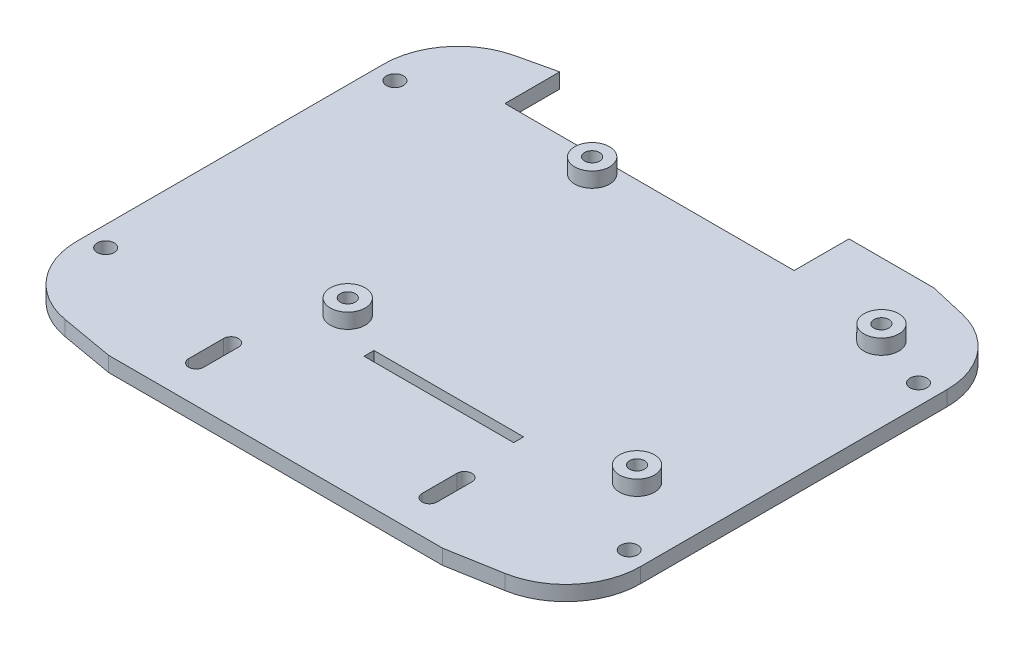
SolidWorks part; units mm, degrees
note: The reader was unsure of these and kept them because the rebuilt part matched: shared geometry of "Esquisse8<3>".
ref_plane "Plan de face" through (0, 0, 0) normal (0, 0, 1) x (1, 0, 0)
ref_plane "Plan de dessus" through (0, 0, 0) normal (0, 1, 0) x (1, 0, 0)
ref_plane "Plan de droite" through (0, 0, 0) normal (1, 0, 0) x (0, 0, -1)
sketch "Esquisse1" plane through (0, 0, 0) normal (0, 1, 0) x (1, 0, 0)
  line L0 (-33.922, -73) -> (33.922, -73) construction
  line L3 (-37.5, 95) -> (37.5, 95)
  line L4 (37.5, 51) -> (37.5, 95)
  line L5 (0, 0) -> (37.5, 95) construction
  line L6 (-21, -61.9) -> (-21, -66.9) construction
  line L7 (0, 95) -> (0, -95) construction
  line L8 (37.5, 51) -> (44.8743, 49.2975)
  line L9 (-24, -61.9) -> (-24, -66.9) construction
  line L10 (56.5, 34.682) -> (56.5, -26.8)
  line L11 (44.1047, -41.5721) -> (17, -46.3514)
  line L12 (22.5, -54.5324) -> (22.5, -84.1) construction
  line L13 (42.569, 51.5625) -> (42.569, 95.5625) construction
  line L14 (-8.1306, -79.1) -> (-42.569, -79.1) construction
  line L15 (56.5, -39.3865) -> (56.5, -125.6461) construction
  line L16 (-17, -95) -> (17, -95)
  line L17 (0, 0) -> (18.2122, -46.1377) construction
  line L18 (-56.5, 51) -> (56.5, 51) construction
  line L19 (-8.1306, -66.9) -> (-42.569, -66.9) construction
  line L20 (-33.922, -79.1) -> (-33.922, -66.9) construction
  line L24 (0, 0) -> (-18.2122, -46.1377) construction
  line L25 (-56.5, -39.3865) -> (-56.5, -125.6461) construction
  line L26 (33.922, -79.1) -> (33.922, -66.9) construction
  line L27 (8.1306, -66.9) -> (42.569, -66.9) construction
  line L28 (8.1306, -79.1) -> (42.569, -79.1) construction
  line L29 (17, -66.9) -> (27, -66.9)
  line L30 (27, -66.9) -> (27, -61.9)
  line L31 (27, -61.9) -> (17, -61.9)
  line L32 (24, -61.9) -> (24, -66.9) construction
  line L33 (21, -61.9) -> (21, -66.9) construction
  line L34 (27, -84.1) -> (17, -84.1)
  line L35 (17, -79.1) -> (27, -79.1)
  line L36 (27, -79.1) -> (27, -84.1)
  line L37 (17, -66.9) -> (17, -79.1)
  line L38 (17, -84.1) -> (17, -95)
  line L39 (17, -61.9) -> (17, -46.3514)
  line L40 (-42.569, 51.5625) -> (-42.569, 95.5625) construction
  line L41 (-22.5, -54.5324) -> (-22.5, -84.1) construction
  line L42 (0, 0) -> (-37.5, 95) construction
  line L44 (-17, -61.9) -> (-17, -46.3514)
  line L45 (-17, -84.1) -> (-17, -95)
  line L46 (-17, -66.9) -> (-17, -79.1)
  line L47 (-27, -79.1) -> (-27, -84.1)
  line L48 (-17, -79.1) -> (-27, -79.1)
  line L49 (-27, -84.1) -> (-17, -84.1)
  line L50 (-27, -61.9) -> (-17, -61.9)
  line L51 (-27, -66.9) -> (-27, -61.9)
  line L52 (-17, -66.9) -> (-27, -66.9)
  line L53 (-44.1047, -41.5721) -> (-17, -46.3514)
  line L54 (-56.5, 34.682) -> (-56.5, -26.8)
  line L55 (-37.5, 51) -> (-44.8743, 49.2975)
  line L56 (-37.5, 51) -> (-37.5, 95)
  arc A2 (56.5, -26.8) -> (44.1047, -41.5721) centre (41.5, -26.8) cw
  arc A3 (44.8743, 49.2975) -> (56.5, 34.682) centre (41.5, 34.682) cw
  arc A4 (-44.8743, 49.2975) -> (-56.5, 34.682) centre (-41.5, 34.682) ccw
  arc A5 (-56.5, -26.8) -> (-44.1047, -41.5721) centre (-41.5, -26.8) ccw
  point P0 (0, 0)
  point P16 (0, 51)
  point P33 (33.922, -73)
  point P52 (0, 51)
  point P53 (-56.5, 46.6135)
  point P62 (0, -73)
  point P69 (-33.922, -73)
  point P78 (56.5, 46.6135)
  point P87 (33.922, -73)
  point P88 (-33.922, -73)
  point P89 (56.5, 46.6135)
  dimension "D2" = 10
  dimension "D3" = 190
  dimension "D4" = 34
  dimension "D5" = 13
  dimension "D6" = 56.5
  dimension "D7" = 86
  dimension "D8" = 12.2
  dimension "D9" = 10
  dimension "D10" = 3
  dimension "D11" = 3
  dimension "D16" = 44
extrude "Boss.-Extru.1" add sketch "Esquisse1" along normal blind 3 contours L3 L4 L8 A3 L10 A2 L11 L39 L31 L30 L29 L37 L35 L36 L34 L38 L16 L45 L49 L47 L48 L46 L52 L51 L50 L44 L53 A5 L54 A4 L55 L56
fillet "Congé1" radius 20 2 edges at (17, 1.5, 46.3514) (-17, 1.5, 46.3514)
fillet "Congé2" radius 5 2 edges at (17, 1.5, 61.9) (-17, 1.5, 61.9)
sketch "Esquisse2" plane through (0, 0, 84.1) normal (0, 0, 1) x (1, 0, 0)
  line L0 (0, 17.1398) -> (0, -10.9487) construction
  line L1 (-27, 5) -> (-27, 8.9044)
  line L2 (-27, 8.9044) -> (-16.8331, 8.9044)
  line L3 (-16.8331, 8.9044) -> (-14.4276, 3)
  line L4 (-17, 3) -> (17, 3) construction
  line L6 (-17, 0) -> (17, 0) construction
  line L7 (-14.4276, 0) -> (-27, 0)
  line L8 (-27, 0) -> (-27, 5)
  line L9 (-14.4276, 3) -> (-14.4276, 0)
  line L10 (16.8331, 8.9044) -> (14.4276, 3)
  line L11 (27, 8.9044) -> (16.8331, 8.9044)
  line L12 (27, 5) -> (27, 8.9044)
  line L13 (27, 0) -> (27, 5)
  line L14 (14.4276, 0) -> (27, 0)
  line L15 (14.4276, 3) -> (14.4276, 0)
extrude "Boss.-Extru.2" add sketch "Esquisse2" against normal blind 5
ref_plane "Plan1" through (0, 0, 73) normal (0, 0, 1) x (1, 0, 0)
mirror "Symétrie1" about plane through (0, 0, 73) normal (0, 0, 1) of "Boss.-Extru.2"
fillet "Congé4" radius 2 8 edges at (-16.8331, 8.9044, 81.6) (-14.4276, 3, 81.6) (-16.8331, 8.9044, 64.4) (-14.4276, 3, 64.4) (16.8331, 8.9044, 64.4) (16.8331, 8.9044, 81.6) (14.4276, 3, 64.4) (14.4276, 3, 81.6)
fillet "Congé5" radius 4 10 edges at (27, 8.9044, 81.6) (-27, 8.9044, 81.6) (27, 8.9044, 64.4) (-27, 8.9044, 64.4) (-25.1606, 0, 61.9) (-27, 0, 64.4) (-27, 0, 81.6) (27, 0, 81.6) (27, 0, 64.4) (25.1606, 0, 61.9)
sketch "Esquisse3" plane through (0, 0, 84.1) normal (0, 0, 1) x (1, 0, 0)
  line L0 (-27, 4.4522) -> (-17, 4.4522) construction
  line L3 (-22, 4.4522) -> (-22, 7.1928) construction
  line L4 (0, 9.9913) -> (0, -3.4658) construction
  circle A0 centre (-22, 4.4522) radius 1.5
  circle A1 centre (22, 4.4522) radius 1.5
  dimension "D1" = 3
extrude "Enlèv. mat.-Extru.2" cut sketch "Esquisse3" against normal blind 25
sketch "Esquisse4" plane through (0, 3, 0) normal (0, 1, 0) x (1, 0, 0)
  line L0 (-17, -90.8) -> (17, -90.8) construction
  line L2 (17, -84.1) -> (17, -95) construction
  line L3 (-17, -95) -> (17, -95) construction
  line L4 (-55, -73) -> (55, -73) construction
  line L5 (-8.9067, -81.172) -> (8.9067, -81.172)
  line L6 (-8.9067, -81.172) -> (-8.9067, -64.828)
  line L7 (-8.9067, -64.828) -> (8.9067, -64.828)
  line L8 (8.9067, -81.172) -> (8.9067, -64.828)
  line L9 (-8.9067, -81.172) -> (8.9067, -64.828) construction
  line L10 (-8.9067, -64.828) -> (8.9067, -81.172) construction
  line L11 (0, -87.4088) -> (0, -95) construction
  circle A0 centre (-10, -90.8) radius 1.7
  circle A1 centre (10, -90.8) radius 1.7
  circle A2 centre (8.9067, -64.828) radius 1.7
  circle A3 centre (8.9067, -81.172) radius 1.7
  circle A4 centre (-8.9067, -81.172) radius 1.7
  circle A5 centre (-8.9067, -64.828) radius 1.7
  point P12 (0, -73)
  dimension "D2" = 3.4
  dimension "D3" = 3.4
  dimension "D1" = 4.2
  dimension "D4" = 10
  dimension "D5" = 10
  dimension "D6" = 17.8135
  dimension "D7" = 16.344
extrude "Enlèv. mat.-Extru.3" cut sketch "Esquisse4" against normal blind 25 contours A4 | A3 | A2 | A5 | A0 | A1
sketch "Esquisse5" plane through (0, 3, 0) normal (0, 1, 0) x (1, 0, 0)
  line L0 (37.5, 51) -> (37.5, 95) construction
  line L1 (48.5019, 75) -> (-37.5, 75) construction
  line L2 (39.0019, 53) -> (58.0019, 53) construction
  line L3 (39.0019, 53) -> (39.0019, 97) construction
  line L4 (39.0019, 97) -> (58.0019, 97) construction
  line L5 (58.0019, 53) -> (58.0019, 97) construction
  line L6 (39.0019, 53) -> (58.0019, 97) construction
  line L7 (39.0019, 97) -> (58.0019, 53) construction
  line L8 (-37.5, 51) -> (-37.5, 95) construction
  line L9 (-37.5, 95) -> (37.5, 95) construction
  line L10 (15.5, 75) -> (15.5, 83) construction
  line L11 (27.5, 95) -> (27.5, 38.0482) construction
  line L12 (15.5, 75) -> (15.5, 49) construction
  line L13 (-27.5, 95) -> (-27.5, 53) construction
  line L14 (-13, 83) -> (-13, 67) construction
  line L15 (-13, 83) -> (15.5, 83) construction
  line L16 (-27.5, 89) -> (27.5, 89) construction
  circle A0 centre (15.5, 83) radius 1.7
  circle A1 centre (15.5, 49) radius 1.7
  circle A2 centre (-13, 83) radius 1.7
  circle A3 centre (-13, 67) radius 1.7
  circle A4 centre (27.5, 80) radius 1.7
  circle A5 centre (27.5, 55) radius 1.7
  circle A6 centre (27.5, 89) radius 1.7
  circle A7 centre (-27.5, 89) radius 1.7
  circle A8 centre (-27.5, 80) radius 1.7
  circle A9 centre (-27.5, 55) radius 1.7
  circle A10 centre (0, 89) radius 1.7
  point P3 (48.5019, 75)
  point P26 (-13, 75)
  dimension "D5" = 26
  dimension "D7" = 3.4
  dimension "D10" = 22
  dimension "D13" = 10
  dimension "D14" = 6
  dimension "D16" = 40
  dimension "D17" = 6
  dimension "D20" = 3.4
  dimension "D1" = 75
  dimension "D2" = 19
  dimension "D3" = 44
  dimension "D4" = 20
  dimension "D6" = 28.5
  dimension "D8" = 8
  dimension "D9" = 16
  dimension "D11" = 24.5
  dimension "D12" = 10
  dimension "D15" = 15
  dimension "D18" = 15
  dimension "D19" = 40
extrude "Enlèv. mat.-Extru.4" cut sketch "Esquisse5" against normal blind 10
sketch "Esquisse6" plane through (0, 3, 0) normal (0, 1, 0) x (1, 0, 0)
  line L0 (-52.4847, -25.059) -> (-52.4847, 32.941) construction
  line L1 (-56.5, 34.682) -> (-56.5, -26.8) construction
  line L2 (-56.5, 3.941) -> (56.5, 3.941) construction
  line L3 (56.5, 34.682) -> (56.5, -26.8) construction
  line L4 (0, 53.7621) -> (0, -51.3081) construction
  line L5 (52.4847, -25.059) -> (52.4847, 32.941) construction
  circle A0 centre (-52.4847, 32.941) radius 1.7
  circle A1 centre (-52.4847, -25.059) radius 1.7
  circle A2 centre (52.4847, -25.059) radius 1.7
  circle A3 centre (52.4847, 32.941) radius 1.7
  point P9 (-52.4847, 3.941)
  dimension "D2" = 3.4
  dimension "D1" = 58
extrude "Enlèv. mat.-Extru.5" cut sketch "Esquisse6" against normal blind 10
fillet "Congé6" radius 10 2 edges at (-37.5, 1.5, -95) (37.5, 1.5, -95)
sketch "Esquisse7" plane through (0, 3, 0) normal (0, 1, 0) x (1, 0, 0)
  line L0 (-86.4549, 51) -> (-37.5, 51)
  line L1 (-86.4549, 51) -> (-47.0507, 103.2271)
  line L2 (-47.0507, 103.2271) -> (68.271, 103.2271)
  line L3 (68.271, 103.2271) -> (91.5248, 51)
  line L4 (-37.5, 51) -> (-37.5, 40)
  line L5 (20.5, 51) -> (20.5, 40)
  line L6 (-37.5, 40) -> (20.5, 40)
  line L7 (20.5, 51) -> (91.5248, 51)
  line L8 (-33.4885, -43.444) -> (33.4885, -43.444)
  line L9 (33.4885, -43.444) -> (53.128, -56.1621)
  line L10 (53.128, -56.1621) -> (47.4978, -107.9067)
  line L11 (47.4978, -107.9067) -> (-41.2455, -107.9067)
  line L12 (-41.2455, -107.9067) -> (-59.4767, -77.0744)
  line L13 (-59.4767, -77.0744) -> (-33.4885, -43.444)
  dimension "D1" = 11
  dimension "D2" = 17
extrude "Enlèv. mat.-Extru.8" cut sketch "Esquisse7" against normal mid plane 20
sketch "Esquisse8" plane through (0, 3, 0) normal (0, 1, 0) x (1, 0, 0)
  line L0 (0, -16) -> (0, 40) construction
  line L1 (-56.5, 12) -> (56.5, 12) construction
  line L2 (56.5, -16) -> (-56.5, -16) construction
  line L3 (56.5, 34.682) -> (56.5, -26.8) construction
  line L4 (-56.5, 34.682) -> (-56.5, -26.8) construction
  line L5 (20.5, 40) -> (-37.5, 40) construction
  line L6 (0, 40) -> (0, -16) construction
  line L7 (-16.5, 36.5) -> (41.5, 36.5) construction
  line L8 (-16.5, 36.5) -> (-16.5, -12.5) construction
  line L9 (-16.5, -12.5) -> (41.5, -12.5) construction
  line L10 (41.5, 36.5) -> (41.5, -12.5) construction
  line L11 (-16.5, 36.5) -> (41.5, -12.5) construction
  line L12 (-16.5, -12.5) -> (41.5, 36.5) construction
  line L13 (-45, 40) -> (45, 40) construction
  line L14 (-45, 40) -> (-45, -16) construction
  line L15 (-45, -16) -> (45, -16) construction
  line L16 (45, 40) -> (45, -16) construction
  line L17 (-45, 40) -> (45, -16) construction
  line L18 (-45, -16) -> (45, 40) construction
  line L19 (45, 12) -> (-45, 12) construction
  line L20 (0, -18) -> (0, -43.444) construction
  line L21 (22.2657, -16) -> (-7.7343, -16)
  line L22 (22.2657, -16) -> (22.2657, -18)
  line L23 (22.2657, -18) -> (-7.7343, -18)
  line L24 (-7.7343, -16) -> (-7.7343, -18)
  line L25 (-33.4885, -43.444) -> (33.4885, -43.444) construction
  circle A0 centre (41.5, 36.5) radius 1.5
  circle A1 centre (41.5, -12.5) radius 1.5
  circle A2 centre (-16.5, -12.5) radius 1.5
  circle A3 centre (-16.5, 36.5) radius 1.5
  circle A4 centre (41.5, -12.5) radius 3.5
  circle A5 centre (41.5, 36.5) radius 3.5
  circle A6 centre (-16.5, -12.5) radius 3.5
  circle A7 centre (-16.5, 36.5) radius 3.5
  point P13 (12.5, 12)
  point P24 (0, 12)
  point P32 (0, 12)
  point P43 (0, -18)
  dimension "D4" = 3
  dimension "D1" = 56
  dimension "D2" = 58
  dimension "D3" = 49
  dimension "D5" = 90
  dimension "D6" = 56
  dimension "D7" = 3.5
  dimension "D8" = 2
  dimension "D9" = 30
extrude "Enlèv. mat.-Extru.10" cut sketch "Esquisse8" against normal mid plane 20 contours A0 | L21 L24 L23 L22 | A2 | A3 | A1
extrude "Boss.-Extru.3" add sketch "Esquisse8<3>" along normal blind 3 contours A6 A2 | A4 A1 | A5 A0 | A7 A3
sketch "Esquisse8<3>" plane through (0, 3, 0) normal (0, 1, 0) x (1, 0, 0) same geometry as "Esquisse8"
sketch "Esquisse10" plane through (0, 3, 0) normal (0, 1, 0) x (1, 0, 0)
  line L0 (0, -43.444) -> (0, -18) construction
  line L1 (-33.4885, -43.444) -> (33.4885, -43.444) construction
  line L2 (-7.7343, -18) -> (22.2657, -18) construction
  line L3 (-23.4, -36) -> (0, -36) construction
  line L4 (-23.4, -36) -> (-23.4, -29) construction
  line L5 (-24.9, -36) -> (-24.9, -29)
  line L6 (-21.9, -36) -> (-21.9, -29)
  line L7 (23.4, -36) -> (23.4, -29) construction
  line L8 (24.9, -36) -> (24.9, -29)
  line L9 (21.9, -36) -> (21.9, -29)
  arc A2 (-24.9, -36) -> (-21.9, -36) centre (-23.4, -36) ccw
  arc A3 (-21.9, -29) -> (-24.9, -29) centre (-23.4, -29) ccw
  arc A4 (24.9, -36) -> (21.9, -36) centre (23.4, -36) cw
  arc A5 (21.9, -29) -> (24.9, -29) centre (23.4, -29) cw
  point P10 (0, -30.722)
  point P12 (23.4, -32.5)
  point P13 (-23.4, -32.5)
  dimension "D4" = 1.5
  dimension "D3" = 18
  dimension "D5" = 7
extrude "Enlèv. mat.-Extru.11" cut sketch "Esquisse10" against normal mid plane 13
